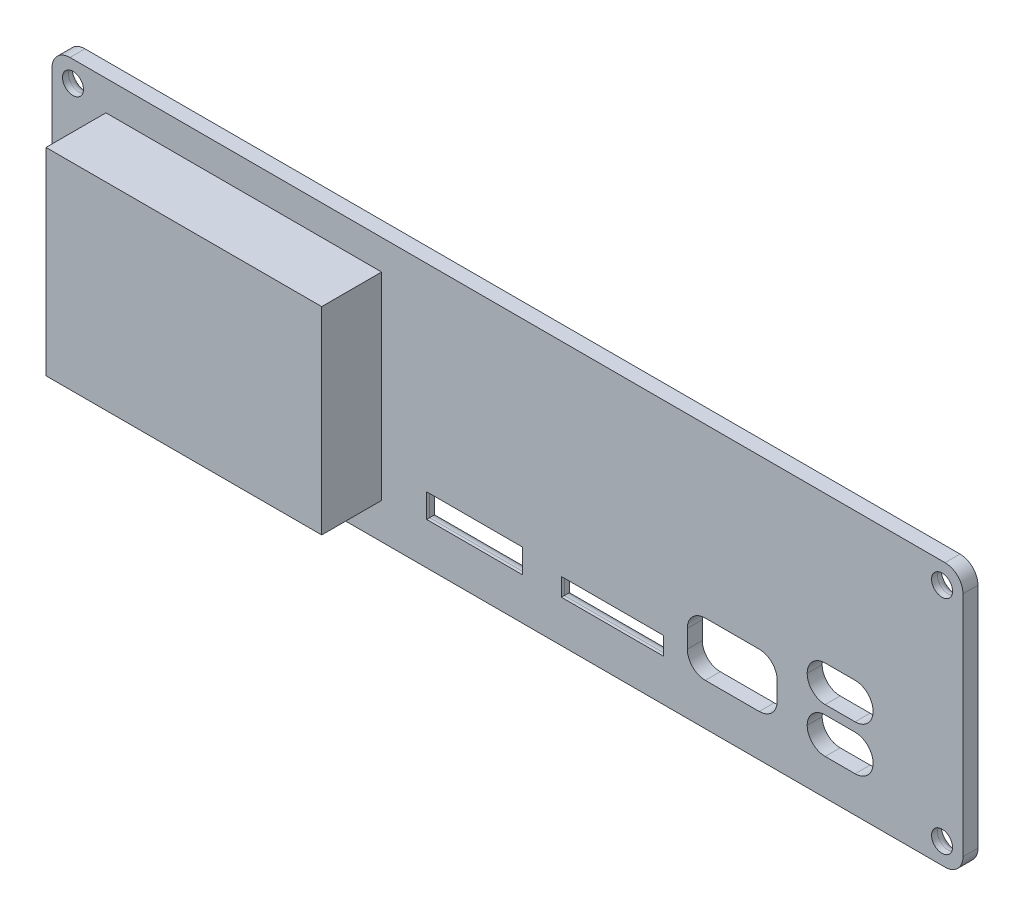
SolidWorks part; units mm, degrees
ref_plane "Front Plane" through (0, 0, 0) normal (0, 0, 1) x (1, 0, 0)
ref_plane "Top Plane" through (0, 0, 0) normal (0, 1, 0) x (1, 0, 0)
ref_plane "Right Plane" through (0, 0, 0) normal (1, 0, 0) x (0, 0, -1)
sketch "Sketch1" plane through (0, 0, 0) normal (0, 0, 1) x (1, 0, 0)
  line L1 (76, -22) -> (-76, -22)
  line L2 (76, -22) -> (76, 22)
  line L3 (76, 22) -> (-76, 22)
  line L4 (-76, -22) -> (-76, 22)
  line L5 (76, -22) -> (-76, 22) construction
  line L6 (76, 22) -> (-76, -22) construction
  point P0 (0, 0)
  dimension "D1" = 152
  dimension "D2" = 44
extrude "main_body" add sketch "Sketch1" along normal blind 2.5
fillet "body_corners" radius 3 4 edges at (-76, -22, 1.25) (76, -22, 1.25) (76, 22, 1.25) (-76, 22, 1.25)
sketch "Sketch2" plane through (0, 0, 2.5) normal (0, 0, 1) x (1, 0, 0)
  line L0 (-76, 18.5) -> (76, 18.5) construction
  line L1 (-76, 19) -> (-76, -19) construction
  line L2 (76, -19) -> (76, 19) construction
  line L3 (-72.5, 22) -> (-72.5, -22) construction
  line L4 (-76, -18.5) -> (76, -18.5) construction
  line L8 (73, 22) -> (-73, 22) construction
  line L9 (72.5, 22) -> (72.5, -22) construction
  line L10 (-73, -22) -> (73, -22) construction
  circle A1 centre (-72.5, -18.5) radius 1.75
  circle A2 centre (72.5, 18.5) radius 1.75
  circle A3 centre (72.5, -18.5) radius 1.75
  circle A4 centre (-72.5, 18.5) radius 1.75
  dimension "D5" = 3.5
  dimension "D6" = 3.5
  dimension "D7" = 3.5
  dimension "D8" = 3.5
  dimension "D1" = 3.5
  dimension "D2" = 3.5
  dimension "D3" = 3.5
  dimension "D4" = 3.5
extrude "mounting_holes" cut sketch "Sketch2" against normal through all
fillet "bolt_heads" radius 1.5 4 edges at (-70.75, -18.5, 0) (-70.75, 18.5, 0) (74.25, -18.5, 0) (74.25, 18.5, 0)
sketch "Sketch3" plane through (0, 0, 2.5) normal (0, 0, 1) x (1, 0, 0)
  line L0 (-76, 5) -> (76, 5) construction
  line L1 (-76, 19) -> (-76, -19) construction
  line L2 (76, -19) -> (76, 19) construction
  line L3 (73, 22) -> (-73, 22) construction
  line L4 (-73, -22) -> (73, -22) construction
  line L5 (0, 22) -> (0, -22) construction
  line L6 (76, -19) -> (76, 19) construction
  line L8 (50, -2.5) -> (61, -2.5)
  line L10 (50, -2.5) -> (50, -8.5)
  line L11 (50, -8.5) -> (61, -8.5)
  line L13 (61, -2.5) -> (61, -8.5)
  line L14 (50, -2.5) -> (61, -8.5) construction
  line L16 (50, -8.5) -> (61, -2.5) construction
  line L17 (30, -6) -> (45, -6)
  line L18 (30, -6) -> (30, -15)
  line L19 (30, -15) -> (45, -15)
  line L20 (45, -6) -> (45, -15)
  line L21 (30, -6) -> (45, -15) construction
  line L22 (30, -15) -> (45, -6) construction
  line L23 (50, -10) -> (61, -10)
  line L24 (50, -10) -> (50, -16)
  line L25 (50, -16) -> (61, -16)
  line L26 (61, -10) -> (61, -16)
  line L27 (50, -10) -> (61, -16) construction
  line L28 (50, -16) -> (61, -10) construction
  line L29 (9, -12) -> (26, -12)
  line L30 (9, -12) -> (9, -15)
  line L31 (9, -15) -> (26, -15)
  line L32 (26, -12) -> (26, -15)
  line L33 (9, -12) -> (26, -15) construction
  line L34 (9, -15) -> (26, -12) construction
  line L35 (-13.5, -11) -> (2.5, -11)
  line L36 (-13.5, -11) -> (-13.5, -15)
  line L37 (-13.5, -15) -> (2.5, -15)
  line L38 (2.5, -11) -> (2.5, -15)
  line L39 (-13.5, -11) -> (2.5, -15) construction
  line L40 (-13.5, -15) -> (2.5, -11) construction
  point P14 (55.5, -4.5)
  point P15 (-5.5, -13)
  point P34 (55.5, -13)
  point P36 (55.5, -5.5)
  point P41 (37.5, -10.5)
  point P49 (55.5, -16)
  point P51 (17.5, -13.5)
  dimension "D7" = 73.5
  dimension "D8" = 7
  dimension "D9" = 4
  dimension "D10" = 16
  dimension "D12" = 50
  dimension "D13" = 6
  dimension "D14" = 11
  dimension "D15" = 31
  dimension "D1" = 17
  dimension "D16" = 6
  dimension "D17" = 15
  dimension "D18" = 15
  dimension "D19" = 11
  dimension "D20" = 6
  dimension "D21" = 15
  dimension "D22" = 9
  dimension "D23" = 7.5
  dimension "D25" = 13.5
  dimension "D26" = 7
  dimension "D28" = 7
  dimension "D30" = 3
  dimension "D31" = 17
extrude "connectors" cut sketch "Sketch3" against normal through all
fillet "usb_host_corners" radius 3 4 edges at (45, -15, 1.25) (45, -6, 1.25) (30, -15, 1.25) (30, -6, 1.25)
fillet "usb_dfu_corners" radius 3 8 edges at (61, -2.5, 1.25) (61, -8.5, 1.25) (50, -8.5, 1.25) (50, -2.5, 1.25) (61, -10, 1.25) (61, -16, 1.25) (50, -16, 1.25) (50, -10, 1.25)
fillet "Fillet1" radius 2 8 edges at (-5.5, -11, 0) (-13.5, -13, 0) (-5.5, -15, 0) (2.5, -13, 0) (9, -13.5, 0) (26, -13.5, 0) (17.5, -15, 0) (17.5, -12, 0)
sketch "Sketch4" plane through (0, 0, 2.5) normal (0, 0, 1) x (1, 0, 0)
  line L0 (-76, 19) -> (-76, -19) construction
  line L1 (-67, 17) -> (-21, 17)
  line L2 (-67, 17) -> (-67, -16)
  line L3 (-67, -16) -> (-21, -16)
  line L4 (-21, 17) -> (-21, -16)
  line L5 (-67, 17) -> (-21, -16) construction
  line L6 (-67, -16) -> (-21, 17) construction
  line L7 (-73, -22) -> (73, -22) construction
  point P0 (-44, 0.5)
  dimension "D1" = 9
  dimension "D2" = 6
  dimension "D3" = 33
  dimension "D4" = 46
extrude "keyer" add sketch "Sketch4" along normal blind 10
sketch "Sketch5" plane through (0, 0, 12.5) normal (0, 0, 1) x (1, 0, 0)
  line L0 (-67, -16) -> (-21, 17) construction
  line L1 (-21, 17) -> (-67, 17) construction
  line L2 (-22, -15) -> (-66, -15)
  line L3 (-67, 17) -> (-21, -16) construction
  line L4 (-22, -15) -> (-22, 16)
  line L5 (-22, 16) -> (-66, 16)
  line L6 (-66, -15) -> (-66, 16)
  line L7 (-22, -15) -> (-66, 16) construction
  line L8 (-22, 16) -> (-66, -15) construction
  line L9 (-21, -16) -> (-21, 17) construction
  point P4 (-44, 0.5)
  dimension "D1" = 1
  dimension "D2" = 1
extrude "keyer_cut" cut sketch "Sketch5" against normal through all from offset 1 offset against normal yes
